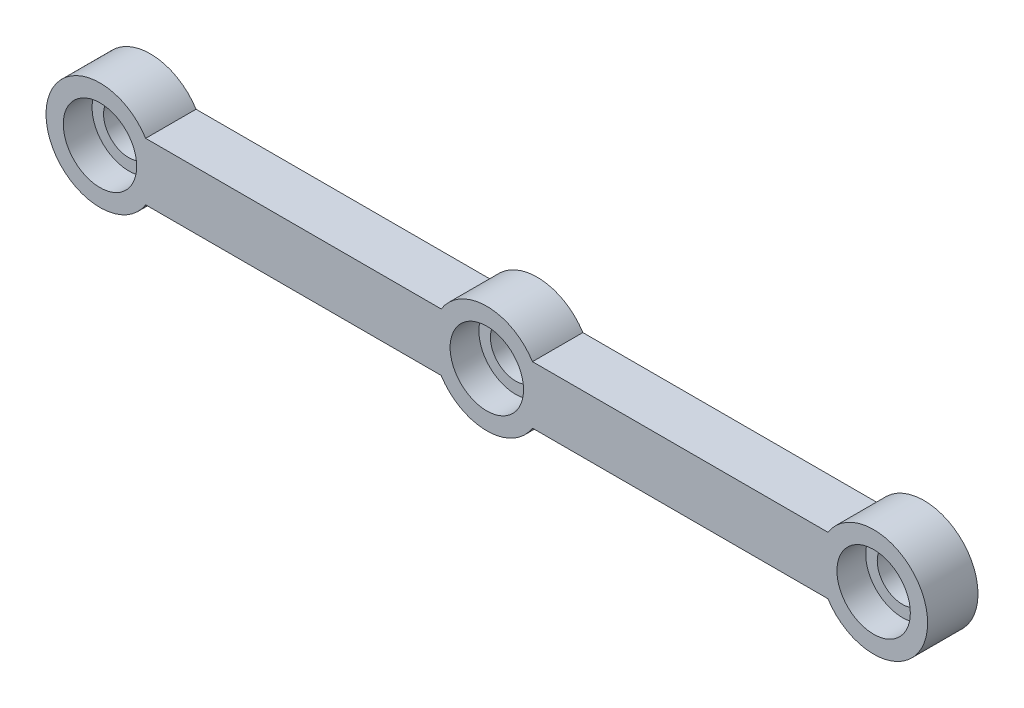
SolidWorks part; units mm, degrees
ref_plane "Front Plane" through (0, 0, 0) normal (0, 0, 1) x (1, 0, 0)
ref_plane "Top Plane" through (0, 0, 0) normal (0, 1, 0) x (1, 0, 0)
ref_plane "Right Plane" through (0, 0, 0) normal (1, 0, 0) x (0, 0, -1)
sketch "Sketch1" plane through (0, 0, 0) normal (0, 0, 1) x (1, 0, 0)
  line L1 (-60, -4) -> (60, -4)
  line L2 (-60, -4) -> (-60, 4)
  line L3 (-60, 4) -> (60, 4)
  line L4 (60, -4) -> (60, 4)
  line L5 (-60, -4) -> (60, 4) construction
  line L6 (-60, 4) -> (60, -4) construction
  circle A0 centre (0, 0) radius 1.5
  point P0 (0, 0)
  dimension "D3" = 3
  dimension "D1" = 8
  dimension "D2" = 120
extrude "Boss-Extrude1" add sketch "Sketch1" along normal blind 3
fillet "Fillet2" radius 4 1 edges at (-60, 4, 1.5)
fillet "Fillet3" radius 4 1 edges at (-60, -4, 1.5)
fillet "Fillet4" radius 4 2 edges at (60, -4, 1.5) (60, 4, 1.5)
sketch "Sketch2" plane through (0, 0, 3) normal (0, 0, 1) x (1, 0, 0)
  line L0 (56, 4) -> (-56, 4) construction
  line L1 (-56, -4) -> (56, -4) construction
  circle A0 centre (-53.7386, 0) radius 1.5
  circle A1 centre (53.7386, 0) radius 1.5
  circle A2 centre (0, 0) radius 1.5 construction
  dimension "D1" = 3
  dimension "D2" = 3
  dimension "D3" = 107.4772
  dimension "D4" = 53.7386
  dimension "D5" = 4
  dimension "D6" = 4
extrude "Cut-Extrude1" cut sketch "Sketch2" against normal blind 3
sketch "Sketch3" plane through (0, 0, 3) normal (0, 0, 1) x (1, 0, 0)
  line L0 (56, 4) -> (-56, 4) construction
  line L1 (56, 4) -> (53.7386, 4)
  line L3 (0, 0) -> (0, 18.9052) construction
  line L4 (-53.7386, -4) -> (-56, -4)
  line L5 (53.7386, -4) -> (56, -4)
  line L6 (-56, 4) -> (-53.7386, 4)
  arc A1 (53.7386, -4) -> (53.7386, 4) centre (53.7386, 0) ccw
  arc A2 (60, 0) -> (56, 4) centre (56, 0) ccw construction
  arc A3 (60, 0) -> (56, 4) centre (56, 0) ccw
  arc A4 (56, -4) -> (60, 0) centre (56, 0) ccw construction
  arc A5 (56, -4) -> (60, 0) centre (56, 0) ccw
  arc A6 (-60, 0) -> (-56, 4) centre (-56, 0) cw
  arc A7 (-56, -4) -> (-60, 0) centre (-56, 0) cw
  arc A8 (-53.7386, -4) -> (-53.7386, 4) centre (-53.7386, 0) cw
  line M9 (-56, -4) -> (56, -4)
  arc M10 (56, -4) -> (60, 0) centre (56, 0) ccw
  arc M11 (60, 0) -> (56, 4) centre (56, 0) ccw
  line M12 (56, 4) -> (-56, 4)
  arc M13 (-56, 4) -> (-60, 0) centre (-56, 0) ccw
  arc M14 (-60, 0) -> (-56, -4) centre (-56, 0) ccw
  dimension "D1" = 8
extrude "Cut-Extrude2" cut sketch "Sketch3" against normal blind 3 contours A8 M9 M12 M13 M14 | A1 M9 M10 M11 M12 region at (58.0109, 0, 3) region at (-58.0109, 0, 3) body kept at (-53.7386, -4, 0)
sketch "Sketch4" plane through (0, 0, 0) normal (0, 0, -1) x (-1, 0, 0)
  line L2 (53.7386, 4) -> (-53.7386, 4)
  line L3 (-53.7386, -4) -> (53.7386, -4)
  line L4 (53.7386, 4) -> (-53.7386, 4)
  line L5 (-53.7386, -4) -> (53.7386, -4)
  arc A2 (53.7386, -4) -> (53.7386, 4) centre (53.7386, 0) ccw
  arc A3 (-53.7386, 4) -> (-53.7386, -4) centre (-53.7386, 0) ccw
  arc A4 (53.7386, -4) -> (53.7386, 4) centre (53.7386, 0) ccw
  arc A5 (-53.7386, 4) -> (-53.7386, -4) centre (-53.7386, 0) ccw
  circle A10 centre (-53.7386, 0) radius 1.5 construction
  circle A11 centre (-53.7386, 0) radius 1.5
  circle A12 centre (0, 0) radius 1.5 construction
  circle A13 centre (0, 0) radius 1.5
  circle A14 centre (53.7386, 0) radius 1.5 construction
  circle A15 centre (53.7386, 0) radius 1.5
  arc M5 (53.7386, -4) -> (53.7386, 4) centre (53.7386, 0) ccw
  line M6 (53.7386, 4) -> (-53.7386, 4)
  arc M7 (-53.7386, 4) -> (-53.7386, -4) centre (-53.7386, 0) ccw
  line M8 (-53.7386, -4) -> (53.7386, -4)
  circle M9 centre (53.7386, 0) radius 1.5
  circle M10 centre (-53.7386, 0) radius 1.5
  circle M11 centre (0, 0) radius 1.5
  dimension "D1" = 0
extrude "Boss-Extrude2" add sketch "Sketch4" along normal blind 4 contours M8 M5 M6 M7 M9 M11 M10 region at (-56.5811, 0, 0)
sketch "Sketch5" plane through (0, 0, 3) normal (0, 0, 1) x (1, 0, 0)
  circle A0 centre (-53.7386, 0) radius 7.5
  circle A1 centre (0, 0) radius 7.5
  circle A2 centre (53.7386, 0) radius 7.5
  circle A3 centre (-53.7386, 0) radius 1.5 construction
  circle A4 centre (-53.7386, 0) radius 1.5
  circle A5 centre (0, 0) radius 1.5 construction
  circle A6 centre (0, 0) radius 1.5
  circle A7 centre (53.7386, 0) radius 1.5 construction
  circle A8 centre (53.7386, 0) radius 1.5
  dimension "D1" = 15
  dimension "D2" = 15
  dimension "D3" = 15
extrude "Boss-Extrude3" add sketch "Sketch5" against normal through all
sketch "Sketch6" plane through (0, 0, 3) normal (0, 0, 1) x (1, 0, 0)
  circle A0 centre (-53.7386, 0) radius 5
  circle A1 centre (0, 0) radius 5
  circle A2 centre (53.7386, 0) radius 5
  dimension "D1" = 10
  dimension "D2" = 10
  dimension "D3" = 10
extrude "Cut-Extrude3" cut sketch "Sketch6" against normal blind 4
sketch "Sketch7" plane through (0, 0, -4) normal (0, 0, -1) x (-1, 0, 0)
  circle A0 centre (-53.7386, 0) radius 3.5
  circle A1 centre (0, 0) radius 3.5
  circle A2 centre (53.7386, 0) radius 3.5
  dimension "D1" = 7
  dimension "D2" = 7
  dimension "D3" = 7
extrude "Cut-Extrude4" cut sketch "Sketch7" against normal blind 4
sketch "Sketch8" plane through (0, 0, 3) normal (0, 0, 1) x (1, 0, 0)
  circle A0 centre (-53.7386, 0) radius 5.1
  circle A1 centre (0, 0) radius 5.1
  circle A2 centre (53.7386, 0) radius 5.1
  circle A3 centre (-53.7386, 0) radius 5
  circle A4 centre (0, 0) radius 5
  circle A5 centre (53.7386, 0) radius 5
  dimension "D1" = 10.2
  dimension "D2" = 10.2
  dimension "D3" = 10.2
  dimension "D4" = 10
  dimension "D5" = 10
  dimension "D6" = 10
extrude "Cut-Extrude5" cut sketch "Sketch8" against normal up to surface (4 mm away) up to face at (-50.2386, 0, -1)
